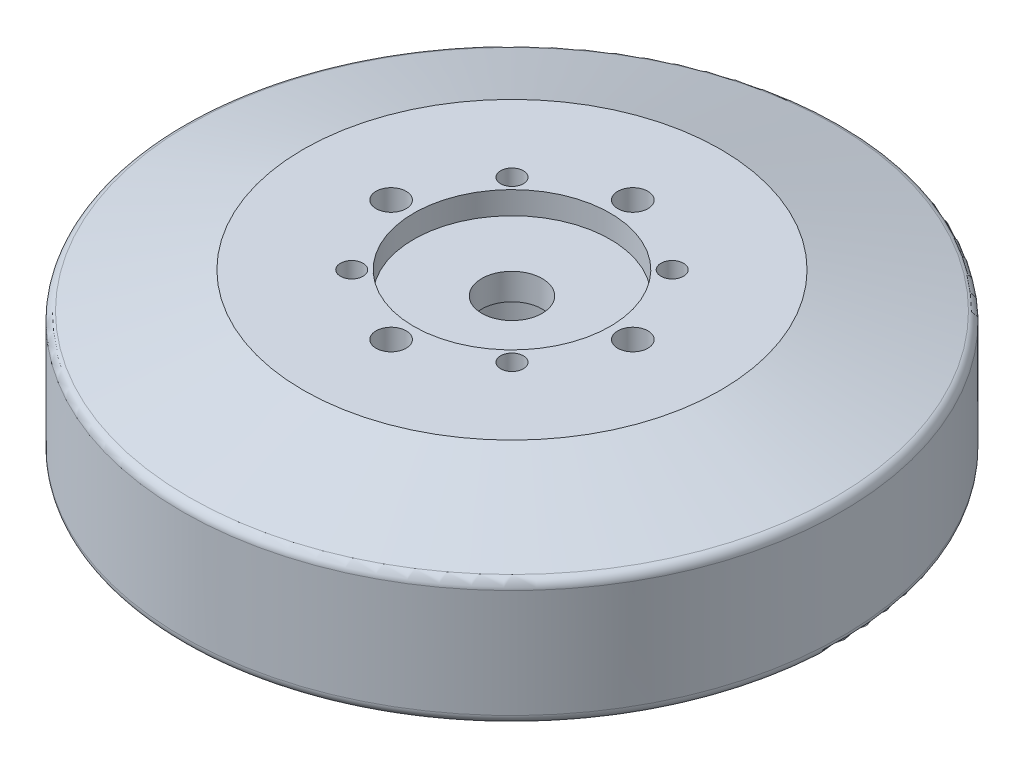
SolidWorks part; units mm, degrees
material "Copper"
ref_plane "Front Plane" through (0, 0, 0) normal (0, 0, 1) x (1, 0, 0)
ref_plane "Top Plane" through (0, 0, 0) normal (0, 1, 0) x (1, 0, 0)
ref_plane "Right Plane" through (0, 0, 0) normal (1, 0, 0) x (0, 0, -1)
sketch "Sketch1" plane through (0, 0, 0) normal (0, 1, 0) x (1, 0, 0)
  circle A0 centre (0, 0) radius 43.625
  dimension "D1" = 87.25
extrude "Boss-Extrude1" add sketch "Sketch1" along normal blind 26.5
chamfer "Chamfer1" distance 5 distance2 16 1 edges at (0, 26.5, 43.625) first distance on face at (0, 26.5, 43.625)
sketch "Sketch2" plane through (0, 26.5, 0) normal (0, 1, 0) x (1, 0, 0)
  line L0 (0, 0) -> (65.3059, 0) construction
  line L1 (0, 0) -> (49.7209, 49.7209) construction
  circle A0 centre (0, 0) radius 16 construction
  circle A1 centre (16, 0) radius 2
  circle A3 centre (10.6066, 10.6066) radius 1.5
  circle A6 centre (0, 0) radius 15 construction
  dimension "D1" = 32
  dimension "D2" = 4
  dimension "D4" = 3
  dimension "D6" = 30
  dimension "D5" = 45
extrude "Cut-Extrude1" cut sketch "Sketch2" against normal blind 6
sketch "Sketch3" plane through (0, 26.5, 0) normal (0, 1, 0) x (1, 0, 0)
  circle A0 centre (0, 0) radius 13
  dimension "D1" = 26
extrude "Cut-Extrude2" cut sketch "Sketch3" against normal blind 3
chamfer "Chamfer2" distance 23 distance2 5.23 1 edges at (0, 0, 43.625) first distance on face at (0, 0, 43.625)
fillet "Fillet1" radius 1.27 2 edges at (0, 5.23, 43.625) (0, 21.5, 43.625)
sketch "Sketch4" plane through (0, 0, 0) normal (0, -1, 0) x (1, 0, 0)
  circle A2 centre (0, 0) radius 6.35
  dimension "D1" = 12.7
sketch "Sketch5" plane through (0, 26.5, 0) normal (0, 1, 0) x (1, 0, 0)
  circle A0 centre (0, 0) radius 4
  dimension "D1" = 8
extrude "Cut-Extrude3" cut sketch "Sketch5" against normal through all
extrude "Cut-Extrude4" cut sketch "Sketch4" against normal blind 20
sketch "Sketch6" plane through (0, 0, 0) normal (0, -1, 0) x (1, 0, 0)
  line L0 (0, 0) -> (0, 36.7175) construction
  line L1 (0, 0) -> (-45.9355, 45.9355) construction
  circle A0 centre (0, 0) radius 17.5 construction
  circle A1 centre (0, 0) radius 12.5 construction
  circle A3 centre (0, 17.5) radius 1.5
  circle A4 centre (0, 12.5) radius 1.5
  circle A5 centre (-12.3744, 12.3744) radius 1.5
  dimension "D1" = 3
  dimension "D3" = 25
  dimension "D4" = 35
  dimension "D2" = 45
extrude "Cut-Extrude5" cut sketch "Sketch6" against normal blind 6
pattern_circular "CirPattern1" count 4 over 360 about axis through (0, 23.5, 0) along (0, 1, 0) of "Cut-Extrude1", "Cut-Extrude5"
ref_axis "Axis1" through (0, 20, 0) along (0, -1, 0)
